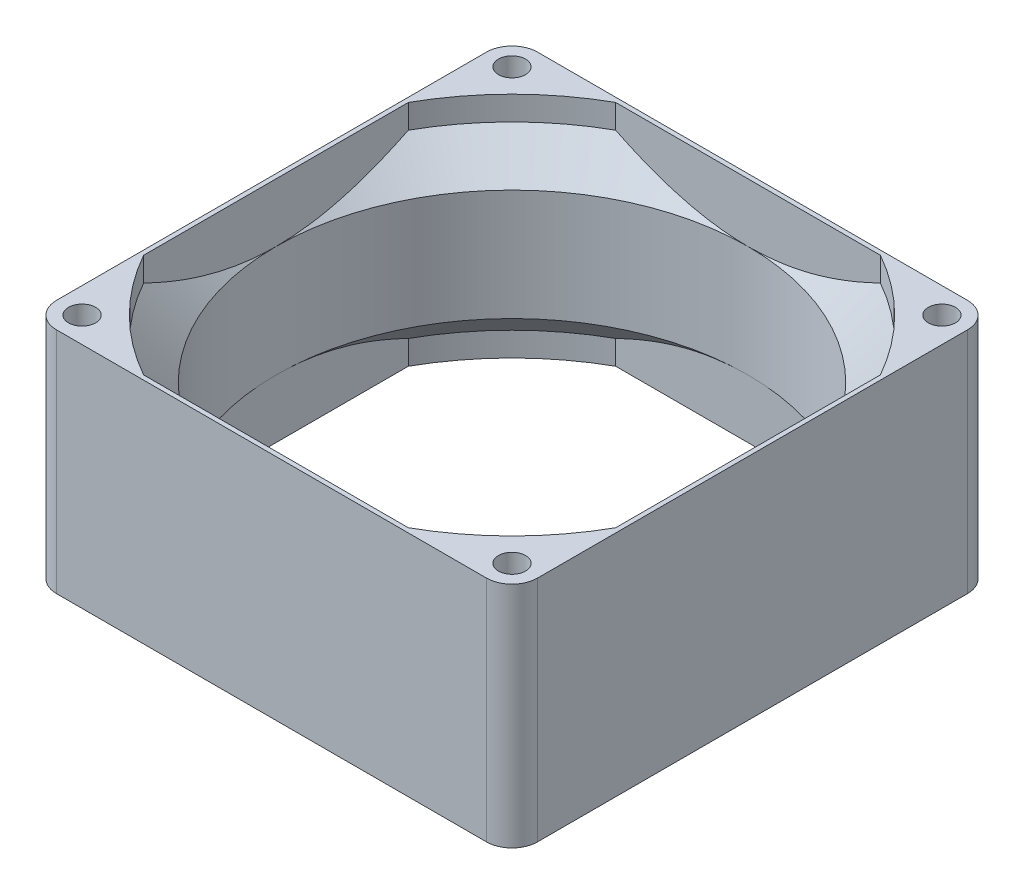
SolidWorks part; units mm, degrees
ref_plane "Front Plane" through (0, 0, 0) normal (0, 0, 1) x (1, 0, 0)
ref_plane "Top Plane" through (0, 0, 0) normal (0, 1, 0) x (1, 0, 0)
ref_plane "Right Plane" through (0, 0, 0) normal (1, 0, 0) x (0, 0, -1)
sketch "Sketch1" plane through (0, 0, 0) normal (0, 1, 0) x (1, 0, 0)
  line L0 (22.0099, 39.25) -> (-22.0099, 39.25)
  line L1 (-35.75, -40) -> (35.75, -40)
  line L2 (-40, -35.75) -> (-40, 35.75)
  line L3 (-35.75, 40) -> (35.75, 40)
  line L4 (40, -35.75) -> (40, 35.75)
  line L5 (-40, -40) -> (40, 40) construction
  line L6 (-40, 40) -> (40, -40) construction
  line L7 (39.25, -22.0099) -> (39.25, 22.0099)
  line L8 (-22.0099, -39.25) -> (22.0099, -39.25)
  line L9 (-39.25, 22.0099) -> (-39.25, -22.0099)
  arc A0 (22.0099, 39.25) -> (39.25, 22.0099) centre (0, 0) cw
  arc A1 (39.25, -22.0099) -> (22.0099, -39.25) centre (0, 0) cw
  arc A2 (-22.0099, -39.25) -> (-39.25, -22.0099) centre (0, 0) cw
  arc A3 (-39.25, 22.0099) -> (-22.0099, 39.25) centre (0, 0) cw
  circle A4 centre (35.75, 35.75) radius 2.25
  circle A5 centre (35.75, -35.75) radius 2.25
  circle A6 centre (-35.75, -35.75) radius 2.25
  circle A7 centre (-35.75, 35.75) radius 2.25
  arc A8 (-35.75, -40) -> (-40, -35.75) centre (-35.75, -35.75) cw
  arc A9 (35.75, -40) -> (40, -35.75) centre (35.75, -35.75) ccw
  arc A10 (35.75, 40) -> (40, 35.75) centre (35.75, 35.75) cw
  arc A11 (-40, 35.75) -> (-35.75, 40) centre (-35.75, 35.75) cw
  point P0 (0, 0)
  point P22 (0, 0)
  point P27 (0, 0)
  dimension "D2" = 45
  dimension "D5" = 4.5
  dimension "D1" = 80
  dimension "D3" = 39.25
  dimension "D7" = 71.5
  dimension "D4" = 4
  dimension "D6" = 4
extrude "Boss-Extrude1" add sketch "Sketch1" along normal blind 38
sketch "Sketch2" plane through (0, 0, 0) normal (1, 0, 0) x (0, 0, -1)
  line L0 (0, 0) -> (0, 29.5169) construction
  line L1 (39.25, 28.25) -> (45, 34)
  line L2 (39.25, 38) -> (39.25, 0) construction
  line L3 (39.25, 28.25) -> (39.25, 9.75)
  line L4 (45, 34) -> (45, 4)
  line L5 (45, 4) -> (39.25, 9.75)
  line L6 (-35.75, 38) -> (35.75, 38) construction
  line L7 (-35.75, 0) -> (35.75, 0) construction
  line L8 (-35.75, 38) -> (35.75, 38)
  line L9 (-35.75, 0) -> (35.75, 0)
  line L10 (39.25, 19) -> (45, 19) construction
  dimension "D1" = 45
  dimension "D2" = 4
  dimension "D3" = 45
revolve "Revolve1" add sketch "Sketch2" angle 360 about L0 region at (0, 19, -42.3522)
sketch "Sketch3" plane through (0, 0, 0) normal (0, 1, 0) x (1, 0, 0)
  line L0 (-40, 35.75) -> (-40, -35.75) construction
  line L1 (-40, 35.75) -> (-40, -35.75)
  line L2 (-35.75, -40) -> (35.75, -40) construction
  line L3 (40, -35.75) -> (40, 35.75) construction
  line L4 (35.75, 40) -> (-35.75, 40) construction
  line L5 (-35.75, -40) -> (35.75, -40)
  line L6 (40, -35.75) -> (40, 35.75)
  line L7 (35.75, 40) -> (-35.75, 40)
  arc A0 (-40, -35.75) -> (-35.75, -40) centre (-35.75, -35.75) ccw construction
  arc A1 (35.75, -40) -> (40, -35.75) centre (35.75, -35.75) ccw construction
  arc A2 (40, 35.75) -> (35.75, 40) centre (35.75, 35.75) ccw construction
  arc A3 (-40, -35.75) -> (-35.75, -40) centre (-35.75, -35.75) ccw
  arc A4 (35.75, -40) -> (40, -35.75) centre (35.75, -35.75) ccw
  arc A5 (40, 35.75) -> (35.75, 40) centre (35.75, 35.75) ccw
  arc A6 (-35.75, 40) -> (-40, 35.75) centre (-35.75, 35.75) ccw construction
  arc A7 (-35.75, 40) -> (-40, 35.75) centre (-35.75, 35.75) ccw
  circle A8 centre (0, 0) radius 54.8081
extrude "Cut-Extrude1" cut sketch "Sketch3" against normal through all both and the other way through all contours A7 A8 A3 L1 | A3 A8 A4 L5 | A4 A8 A5 L6 | A5 A8 A7 L7 region at (-45.9916, 0, 0) region at (0, 0, -45.9916) region at (0, 0, 45.9916) region at (45.9916, 0, 0)
